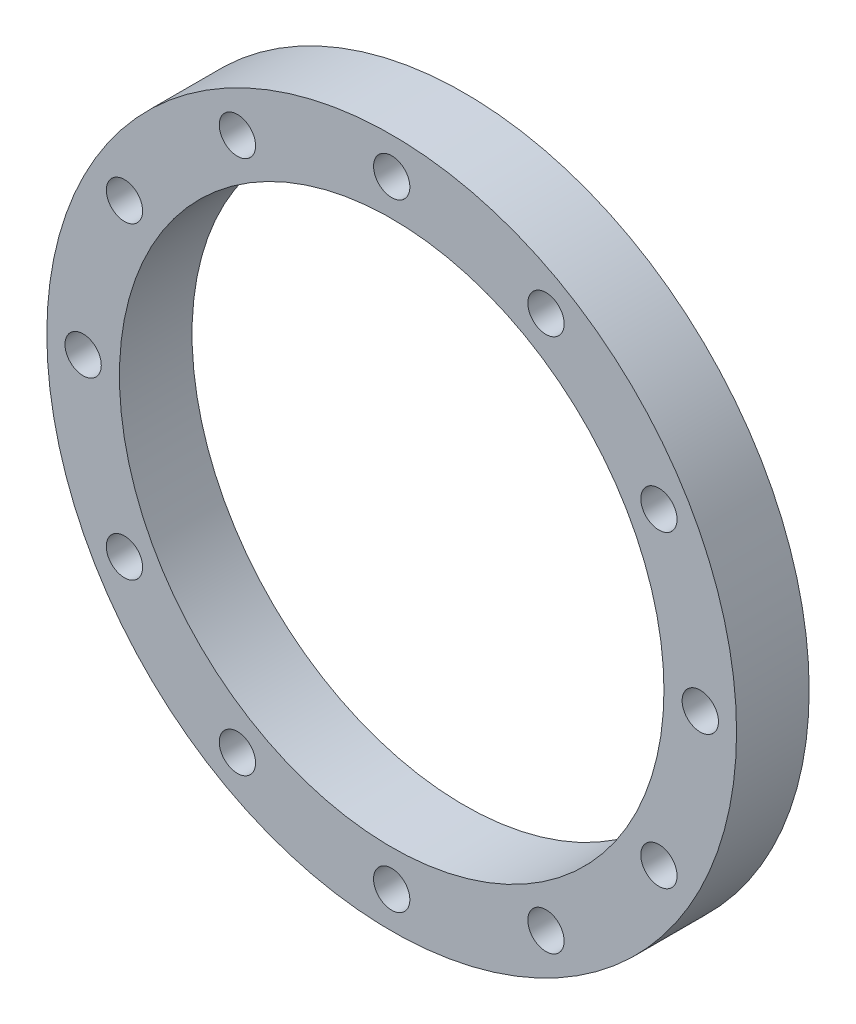
SolidWorks part; units mm, degrees
ref_plane "Front Plane" through (0, 0, 0) normal (0, 0, 1) x (1, 0, 0)
ref_plane "Top Plane" through (0, 0, 0) normal (0, 1, 0) x (1, 0, 0)
ref_plane "Right Plane" through (0, 0, 0) normal (1, 0, 0) x (0, 0, -1)
sketch "Sketch1" plane through (0, 0, 0) normal (0, 0, 1) x (1, 0, 0)
  circle A0 centre (0, 0) radius 241.3
  circle A1 centre (0, 0) radius 190.5
  circle A2 centre (0, 215.9) radius 12.7
  circle A3 centre (0, 0) radius 215.9 construction
  circle A4 centre (107.95, 186.9749) radius 12.7
  circle A5 centre (186.9749, 107.95) radius 12.7
  circle A6 centre (215.9, 0) radius 12.7
  circle A7 centre (186.9749, -107.95) radius 12.7
  circle A8 centre (107.95, -186.9749) radius 12.7
  circle A9 centre (0, -215.9) radius 12.7
  circle A10 centre (-107.95, -186.9749) radius 12.7
  circle A11 centre (-186.9749, -107.95) radius 12.7
  circle A12 centre (-215.9, 0) radius 12.7
  circle A13 centre (-186.9749, 107.95) radius 12.7
  circle A14 centre (-107.95, 186.9749) radius 12.7
  point P32 (0, 0)
  dimension "D1" = 482.6
  dimension "D2" = 381
  dimension "D3" = 431.8
  dimension "D4" = 25.4
  dimension "D5" = 12
extrude "Boss-Extrude1" add sketch "Sketch1" along normal blind 50.8
ref_plane "Plane1" through (0, 0, 25.4) normal (0, 0, -1) x (-1, 0, 0)
sketch "Sketch2" plane through (0, 0, 25.4) normal (0, 0, -1) x (-1, 0, 0)
  line L0 (0, -241.3) -> (0, -368.3)
  line L1 (0, 27.94) -> (0, -27.94) construction
  line L2 (-381, -368.3) -> (381, -368.3) construction
  line L3 (-381, -368.3) -> (-635, -114.3) construction
  line L4 (381, -368.3) -> (381, -114.3) construction
  line L5 (381, -368.3) -> (176.8567, -164.1567)
  line L6 (-381, -368.3) -> (-176.8567, -164.1567)
  circle A0 centre (0, 0) radius 241.3
  dimension "D5" = 482.6
  dimension "D1" = 762
  dimension "D2" = 254
  dimension "D3" = 135
  dimension "D4" = 127
  dimension "D6" = 45
  dimension "D7" = 45
